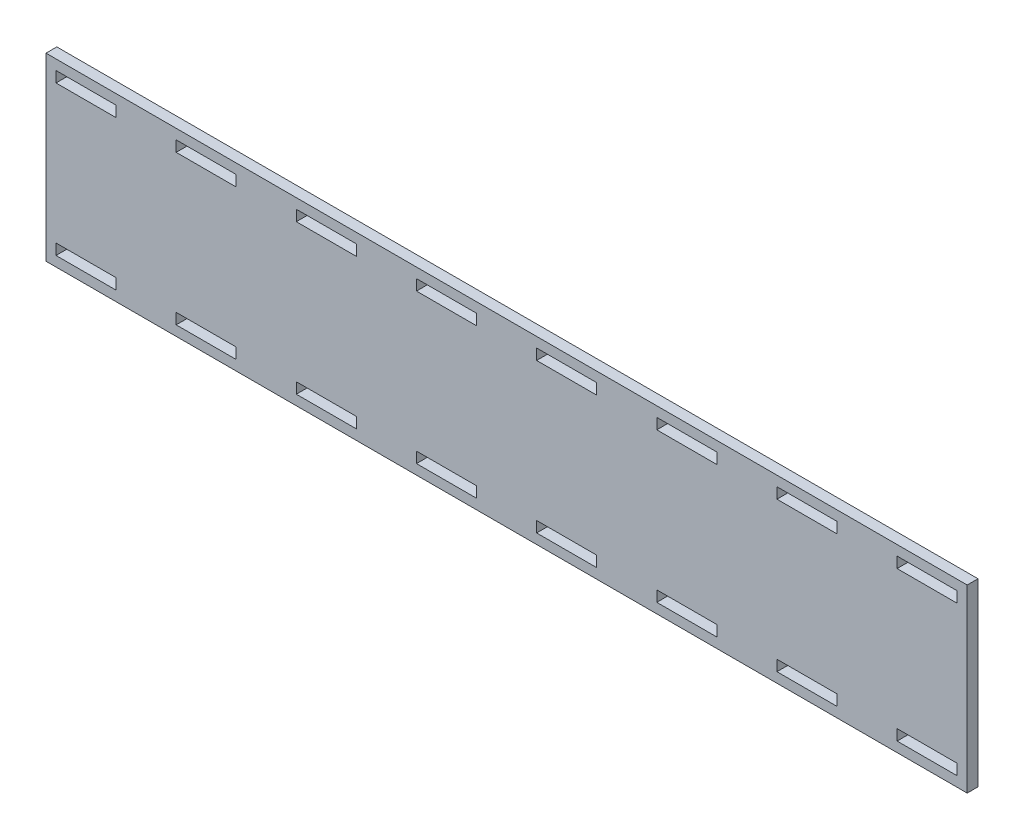
SolidWorks part; units mm, degrees
ref_plane "Front Plane" through (0, 0, 0) normal (0, 0, 1) x (1, 0, 0)
ref_plane "Top Plane" through (0, 0, 0) normal (0, 1, 0) x (1, 0, 0)
ref_plane "Right Plane" through (0, 0, 0) normal (1, 0, 0) x (0, 0, -1)
sketch "Sketch1" plane through (0, 0, 0) normal (0, 0, 1) x (1, 0, 0)
  line L0 (-214.4465, 10.1028) -> (245.5535, 10.1028) construction
  line L1 (-214.4465, 55.1028) -> (245.5535, 55.1028)
  line L2 (-214.4465, 55.1028) -> (-214.4465, -34.8972)
  line L3 (-214.4465, -34.8972) -> (245.5535, -34.8972)
  line L4 (245.5535, 55.1028) -> (245.5535, -34.8972)
  line L9 (-149.4465, 50.1028) -> (-149.4465, 44.7028)
  line L10 (-209.4465, 50.1028) -> (-179.4465, 50.1028)
  line L11 (-209.4465, 50.1028) -> (-209.4465, 44.7028)
  line L12 (-209.4465, 44.7028) -> (-179.4465, 44.7028)
  line L13 (-179.4465, 50.1028) -> (-179.4465, 44.7028)
  line L14 (-149.4465, 50.1028) -> (-119.4465, 50.1028)
  line L15 (-119.4465, 50.1028) -> (-119.4465, 44.7028)
  line L16 (-149.4465, 44.7028) -> (-119.4465, 44.7028)
  line L17 (-89.4465, 50.1028) -> (-89.4465, 44.7028)
  line L18 (-89.4465, 50.1028) -> (-59.4465, 50.1028)
  line L19 (-59.4465, 50.1028) -> (-59.4465, 44.7028)
  line L20 (-89.4465, 44.7028) -> (-59.4465, 44.7028)
  line L21 (-29.4465, 50.1028) -> (-29.4465, 44.7028)
  line L22 (-29.4465, 50.1028) -> (0.5535, 50.1028)
  line L23 (0.5535, 50.1028) -> (0.5535, 44.7028)
  line L24 (-29.4465, 44.7028) -> (0.5535, 44.7028)
  line L25 (30.5535, 50.1028) -> (30.5535, 44.7028)
  line L26 (30.5535, 50.1028) -> (60.5535, 50.1028)
  line L27 (60.5535, 50.1028) -> (60.5535, 44.7028)
  line L28 (30.5535, 44.7028) -> (60.5535, 44.7028)
  line L29 (90.5535, 50.1028) -> (90.5535, 44.7028)
  line L30 (90.5535, 50.1028) -> (120.5535, 50.1028)
  line L31 (120.5535, 50.1028) -> (120.5535, 44.7028)
  line L32 (90.5535, 44.7028) -> (120.5535, 44.7028)
  line L33 (150.5535, 50.1028) -> (150.5535, 44.7028)
  line L34 (150.5535, 50.1028) -> (180.5535, 50.1028)
  line L35 (180.5535, 50.1028) -> (180.5535, 44.7028)
  line L36 (150.5535, 44.7028) -> (180.5535, 44.7028)
  line L37 (210.5535, 50.1028) -> (210.5535, 44.7028)
  line L38 (210.5535, 50.1028) -> (240.5535, 50.1028)
  line L39 (240.5535, 50.1028) -> (240.5535, 44.7028)
  line L40 (210.5535, 44.7028) -> (240.5535, 44.7028)
  line L41 (210.5535, -24.4972) -> (240.5535, -24.4972)
  line L42 (240.5535, -29.8972) -> (240.5535, -24.4972)
  line L43 (210.5535, -29.8972) -> (240.5535, -29.8972)
  line L44 (210.5535, -29.8972) -> (210.5535, -24.4972)
  line L45 (150.5535, -24.4972) -> (180.5535, -24.4972)
  line L46 (180.5535, -29.8972) -> (180.5535, -24.4972)
  line L47 (150.5535, -29.8972) -> (180.5535, -29.8972)
  line L48 (150.5535, -29.8972) -> (150.5535, -24.4972)
  line L49 (90.5535, -24.4972) -> (120.5535, -24.4972)
  line L50 (120.5535, -29.8972) -> (120.5535, -24.4972)
  line L51 (90.5535, -29.8972) -> (120.5535, -29.8972)
  line L52 (90.5535, -29.8972) -> (90.5535, -24.4972)
  line L53 (30.5535, -24.4972) -> (60.5535, -24.4972)
  line L54 (60.5535, -29.8972) -> (60.5535, -24.4972)
  line L55 (30.5535, -29.8972) -> (60.5535, -29.8972)
  line L56 (30.5535, -29.8972) -> (30.5535, -24.4972)
  line L57 (-29.4465, -24.4972) -> (0.5535, -24.4972)
  line L58 (0.5535, -29.8972) -> (0.5535, -24.4972)
  line L59 (-29.4465, -29.8972) -> (0.5535, -29.8972)
  line L60 (-29.4465, -29.8972) -> (-29.4465, -24.4972)
  line L61 (-89.4465, -24.4972) -> (-59.4465, -24.4972)
  line L62 (-59.4465, -29.8972) -> (-59.4465, -24.4972)
  line L63 (-89.4465, -29.8972) -> (-59.4465, -29.8972)
  line L64 (-89.4465, -29.8972) -> (-89.4465, -24.4972)
  line L65 (-149.4465, -24.4972) -> (-119.4465, -24.4972)
  line L66 (-119.4465, -29.8972) -> (-119.4465, -24.4972)
  line L67 (-149.4465, -29.8972) -> (-119.4465, -29.8972)
  line L68 (-179.4465, -29.8972) -> (-179.4465, -24.4972)
  line L69 (-209.4465, -24.4972) -> (-179.4465, -24.4972)
  line L70 (-209.4465, -29.8972) -> (-209.4465, -24.4972)
  line L71 (-209.4465, -29.8972) -> (-179.4465, -29.8972)
  line L72 (-149.4465, -29.8972) -> (-149.4465, -24.4972)
  dimension "D1" = 460
  dimension "D2" = 90
  dimension "D3" = 30
  dimension "D4" = 5.4
  dimension "D5" = 5
  dimension "D6" = 5
  dimension "D7" = 8
extrude "Boss-Extrude1" add sketch "Sketch1" along normal blind 5.4
